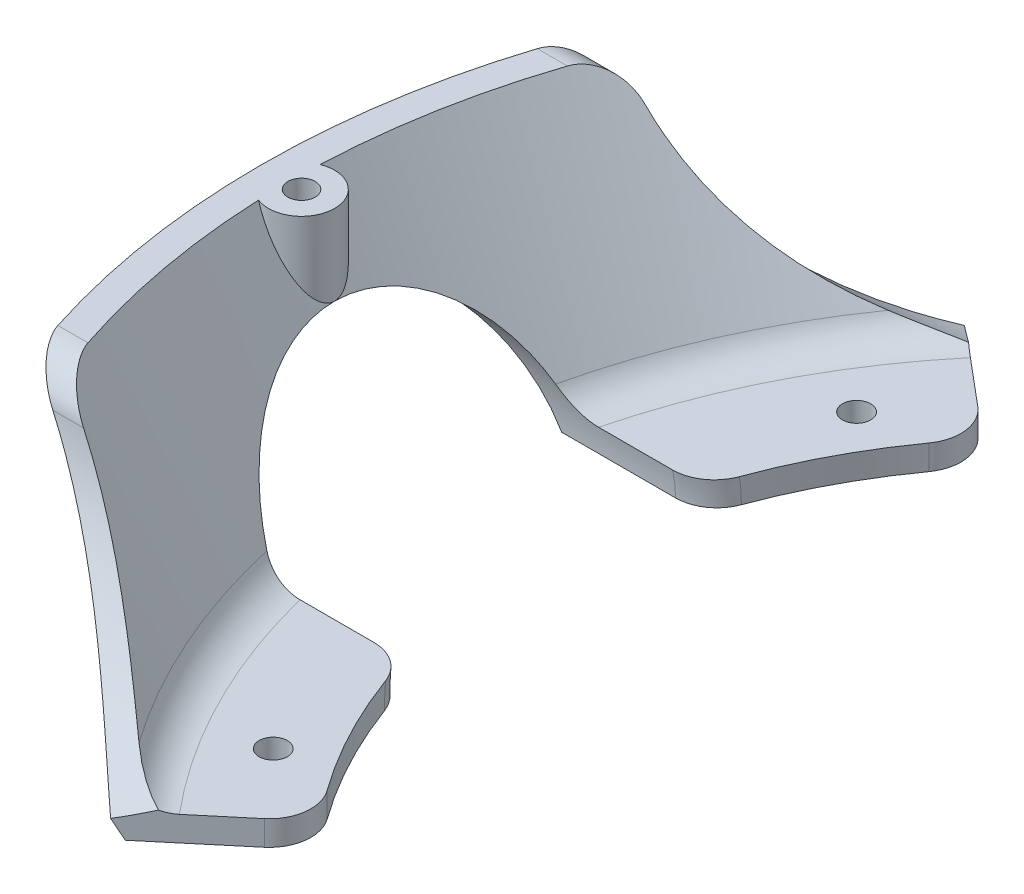
SolidWorks part; units mm, degrees
ref_plane "Plan de face" through (0, 0, 0) normal (0, 0, 1) x (1, 0, 0)
ref_plane "Plan de dessus" through (0, 0, 0) normal (0, 1, 0) x (1, 0, 0)
ref_plane "Plan de droite" through (0, 0, 0) normal (1, 0, 0) x (0, 0, -1)
sketch "Esquisse1" plane through (0, 0, 0) normal (0, 0, 1) x (1, 0, 0)
  line L0 (0, 0) -> (-62.259, 0) construction
  line L1 (-62.259, 0) -> (-79, 0)
  line L2 (-79, 0) -> (-95, 28)
  line L3 (-95, 28) -> (-91.5447, 28)
  line L4 (-91.5447, 28) -> (-77.259, 3)
  line L5 (-77.259, 3) -> (-62.259, 3)
  line L6 (-62.259, 3) -> (-62.259, 0)
  point P3 (-93.2724, 28)
  dimension "D1" = 3
  dimension "D2" = 3
  dimension "D3" = 28
  dimension "D4" = 79
  dimension "D5" = 15
  dimension "D6" = 95
ref_axis "Axe1" through (0, 0, 0) along (0, 1, 0)
revolve "Révolution1" add sketch "Esquisse1" angle 80 mid plane about axis through (0, 0, 0) along (0, 1, 0)
sketch "Esquisse3" plane through (0, 28, 0) normal (0, 1, 0) x (1, 0, 0)
  line L1 (45, 77.9423) -> (-90, 0) construction
  line L2 (-90, 0) -> (45, -77.9423) construction
  line L3 (45, -77.9423) -> (45, 77.9423) construction
  circle A0 centre (0, 0) radius 45 construction
  circle A1 centre (-90, 0) radius 4
  dimension "D2" = 8
  dimension "D1" = 90
extrude "Boss.-Extru.1" add sketch "Esquisse3" against normal blind 20
hole_wizard "Trou pour taraudage pour trou taraudé M41" positions "Esquisse4" profile "Esquisse5" hole size "M4" standard "ISO" end condition through all
sketch "Esquisse4" plane through (0, 28, 0) normal (0, 1, 0) x (1, 0, 0)
  point P3 (-90, 0)
sketch "Esquisse5" plane through (-90, 28, 0) normal (1, 0, 0) x (0, 0, 1)
  line L0 (0, 0) -> (0, 28)
  line L1 (0, 28) -> (1.65, 28)
  line L2 (1.65, 28) -> (1.65, 0)
  line L5 (1.65, 0) -> (0, 0)
  line L11 (0, -6.35) -> (0, 107.95) construction
  dimension "Diamètre du perçage jusqu'au prochain" = 3.3
  dimension "Profondeur du perçage jusqu'au prochain" = 28
hole_wizard "Dégagement M31" positions "Esquisse6" profile "Esquisse7" hole size "M3" standard "ISO" end condition through all
sketch "Esquisse6" plane through (0, 3, 0) normal (0, 1, 0) x (1, 0, 0)
  line L0 (-58.168, 35.25) -> (-1.4434, 68) construction
  line L1 (-1.4434, 68) -> (59.6114, 32.75) construction
  line L2 (59.6114, 32.75) -> (59.6114, -32.75) construction
  line L3 (59.6114, -32.75) -> (-1.4434, -68) construction
  line L4 (-1.4434, -68) -> (-58.168, -35.25) construction
  line L5 (-58.168, -35.25) -> (-58.168, 35.25) construction
  line L7 (-58.168, -35.25) -> (59.6114, -32.75) construction
  line L8 (59.6114, -32.75) -> (-1.4434, 68) construction
  line L9 (-1.4434, 68) -> (-58.168, -35.25) construction
  line L11 (-58.168, 35.25) -> (-1.4434, -68) construction
  line L12 (-1.4434, -68) -> (59.6114, 32.75) construction
  line L13 (59.6114, 32.75) -> (-58.168, 35.25) construction
  line L15 (-58.168, -35.25) -> (29.084, 17.625) construction
  line L17 (-58.168, 35.25) -> (29.084, -17.625) construction
  point P14 (-58.168, 35.25)
  point P24 (-58.168, -35.25)
  point P64 (59.6114, 0)
  dimension "D1" = 65.5
  dimension "D2" = 70.5
sketch "Esquisse7" plane through (-58.168, 3, -35.25) normal (1, 0, 0) x (0, 0, 1)
  line L0 (0, 0) -> (0, 3)
  line L1 (0, 3) -> (1.7, 3)
  line L2 (1.7, 3) -> (1.7, 0)
  line L5 (1.7, 0) -> (0, 0)
  line L11 (0, -6.35) -> (0, 107.95) construction
  dimension "Diamètre du perçage jusqu'au prochain" = 3.4
  dimension "Profondeur du perçage jusqu'au prochain" = 3
sketch "Esquisse8" plane through (0, 0, 0) normal (1, 0, 0) x (0, 0, -1)
  circle A0 centre (-61.0648, 28) radius 27.4781
  circle A1 centre (61.0648, 28) radius 27.4781
  circle A2 centre (0, 0) radius 18.2967
  spline S0 degree 3 poles (-3.7204, 28) (-3.8246, 27.5462) (-3.897, 27.0893) (-3.9879, 26.17) (-4.0061, 25.7062) (-3.9824, 24.3165) (-3.8664, 23.401) (-3.5748, 22.2732) (-3.5088, 22.0485) (-3.3595, 21.6011) (-3.2759, 21.3779) (-2.998, 20.7215) (-2.7774, 20.2981) (-2.3636, 19.6972) (-2.2104, 19.5015) (-1.8731, 19.1374) (-1.689, 18.9679) (-1.2748, 18.6663) (-1.0473, 18.537) (-0.676, 18.3983) (-0.5459, 18.3612) (-0.2836, 18.3111) (-0.1503, 18.2977) (0.2567, 18.2949) (0.5236, 18.3448) (1.023, 18.5248) (1.2516, 18.6521) (1.6693, 18.9511) (1.8551, 19.1199) (2.1954, 19.4834) (2.3496, 19.6785) (2.767, 20.2798) (2.9919, 20.709) (3.3652, 21.587) (3.5126, 22.0346) (3.7482, 22.9422) (3.8363, 23.4046) (3.9576, 24.3294) (3.9908, 24.7907) (4.0059, 25.7113) (3.9878, 26.1706) (3.8973, 27.0869) (3.8251, 27.5441) (3.7204, 28) knots 0 0 0 0 0.0625 0.0625 0.125 0.125 0.25 0.25 0.28125 0.28125 0.3125 0.3125 0.375 0.375 0.40625 0.40625 0.4375 0.4375 0.46875 0.46875 0.484375 0.484375 0.5 0.5 0.53125 0.53125 0.5625 0.5625 0.59375 0.59375 0.625 0.625 0.6875 0.6875 0.75 0.75 0.8125 0.8125 0.875 0.875 0.9375 0.9375 1 1 1 1 construction
extrude "Enlèv. mat.-Extru.1" cut sketch "Esquisse8" against normal through all
fillet "Congé1" radius 5 8 edges at (-87.0128, 28, -33.5868) (-87.0128, 28, 33.5868) (-47.6932, 1.5, -40.0193) (-47.6932, 1.5, 40.0193) (-68.9876, 3, 34.7803) (-68.9876, 3, -34.7803)
